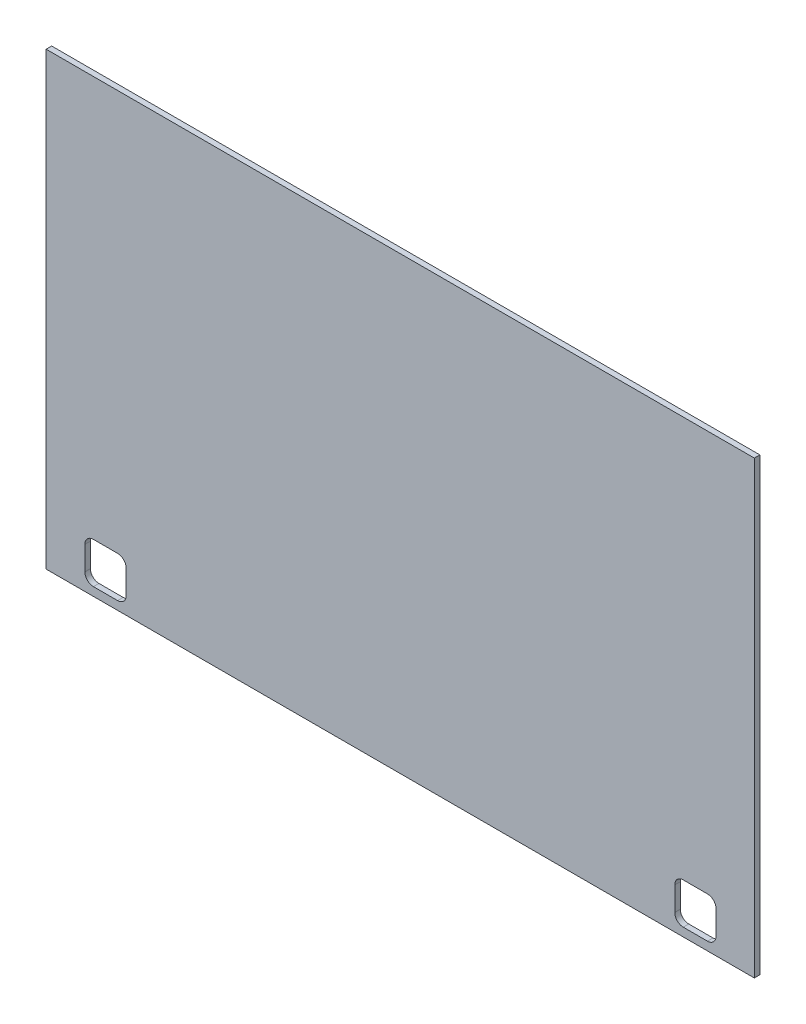
SolidWorks part; units mm, degrees
ref_plane "Plan de face" through (0, 0, 0) normal (0, 0, 1) x (1, 0, 0)
ref_plane "Plan de dessus" through (0, 0, 0) normal (0, 1, 0) x (1, 0, 0)
ref_plane "Plan de droite" through (0, 0, 0) normal (1, 0, 0) x (0, 0, -1)
sketch "Esquisse1" plane through (0, 0, 0) normal (0, 0, 1) x (1, 0, 0)
  line L1 (-416, -264.5) -> (416, -264.5)
  line L2 (-416, -264.5) -> (-416, 264.5)
  line L3 (-416, 264.5) -> (416, 264.5)
  line L4 (416, -264.5) -> (416, 264.5)
  line L5 (-416, -264.5) -> (416, 264.5) construction
  line L6 (-416, 264.5) -> (416, -264.5) construction
  point P0 (0, 0)
  dimension "D1" = 529
  dimension "D2" = 832
extrude "Boss.-Extru.1" add sketch "Esquisse1" along normal blind 6.5
sketch "Esquisse2" plane through (0, 0, 0) normal (0, 0, -1) x (-1, 0, 0)
  line L0 (416, -264.5) -> (-416, -264.5) construction
  line L1 (-361, -254.5214) -> (-332.526, -254.5214)
  line L2 (-371, -244.5214) -> (-371, -216.4752)
  line L3 (-361, -206.4752) -> (-332.526, -206.4752)
  line L4 (-322.526, -244.5214) -> (-322.526, -216.4752)
  line L5 (-371, -254.5214) -> (-322.526, -206.4752) construction
  line L6 (-371, -206.4752) -> (-322.526, -254.5214) construction
  line L7 (-416, -264.5) -> (-416, 264.5) construction
  arc A0 (-322.526, -244.5214) -> (-332.526, -254.5214) centre (-332.526, -244.5214) cw
  arc A1 (-361, -254.5214) -> (-371, -244.5214) centre (-361, -244.5214) cw
  arc A2 (-371, -216.4752) -> (-361, -206.4752) centre (-361, -216.4752) cw
  arc A3 (-322.526, -216.4752) -> (-332.526, -206.4752) centre (-332.526, -216.4752) ccw
  point P0 (-346.763, -230.4983)
  dimension "D1" = 10
  dimension "D2" = 9.9786
  dimension "D3" = 45
  dimension "D4" = 28.0461
extrude "Enlèv. mat.-Extru.1" cut sketch "Esquisse2" against normal through all
ref_axis "Axe1" through (0, 264.5, 0) along (0, -1, 0)
pattern_linear "Répétition linéaire1" count 2 spacing 693 along (-1, 0, 0) of "Enlèv. mat.-Extru.1"
